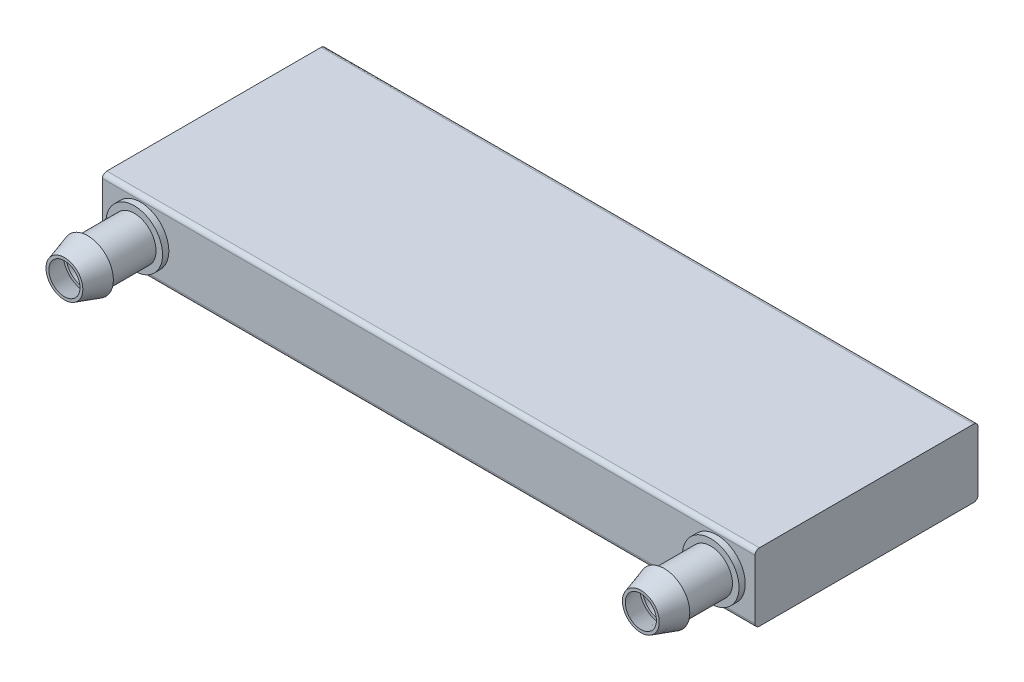
SolidWorks part; units mm, degrees
ref_plane "Front Plane" through (0, 0, 0) normal (0, 0, 1) x (1, 0, 0)
ref_plane "Top Plane" through (0, 0, 0) normal (0, 1, 0) x (1, 0, 0)
ref_plane "Right Plane" through (0, 0, 0) normal (1, 0, 0) x (0, 0, -1)
sketch "Sketch1" plane through (0, 0, 0) normal (0, 1, 0) x (1, 0, 0)
  line L1 (60, -20.5) -> (-60, -20.5)
  line L2 (60, -20.5) -> (60, 20.5)
  line L3 (60, 20.5) -> (-60, 20.5)
  line L4 (-60, -20.5) -> (-60, 20.5)
  line L5 (60, -20.5) -> (-60, 20.5) construction
  line L6 (60, 20.5) -> (-60, -20.5) construction
  point P0 (0, 0)
  dimension "D1" = 41
  dimension "D2" = 120
extrude "Boss-Extrude1" add sketch "Sketch1" along normal blind 12.5
sketch "Sketch2" plane through (0, 0, 20.5) normal (0, 0, 1) x (1, 0, 0)
  line L0 (53, 12.5) -> (53, 0) construction
  line L1 (-60, 12.5) -> (60, 12.5) construction
  line L2 (-60, 0) -> (60, 0) construction
  line L3 (60, 12.5) -> (60, 0) construction
  circle A0 centre (53, 6.25) radius 5.2
  point P8 (52.7193, 6.25)
  dimension "D1" = 10.4
  dimension "D2" = 7
extrude "Boss-Extrude2" add sketch "Sketch2" along normal blind 1.15
sketch "Sketch3" plane through (0, 0, 21.65) normal (0, 0, 1) x (1, 0, 0)
  circle A0 centre (53, 6.25) radius 4
  dimension "D1" = 8
extrude "Boss-Extrude3" add sketch "Sketch3" along normal blind 8.55
sketch "Sketch4" plane through (0, 0, 30.2) normal (0, 0, 1) x (1, 0, 0)
  circle A0 centre (53, 6.25) radius 4.7
  dimension "D1" = 9.4
extrude "Boss-Extrude4" add sketch "Sketch4" along normal blind 4.3 draft 17
mirror "Mirror1" about plane through (0, 0, 0) normal (1, 0, 0) of "Boss-Extrude4", "Boss-Extrude3", "Boss-Extrude2"
fillet "Fillet1" radius 0.8 4 edges at (0, 12.5, -20.5) (0, 12.5, 20.5) (0, 0, 20.5) (0, 0, -20.5)
shell "Shell1" thickness 0.5 removed face at (56.3854, 6.25, 34.5) removed face at (-49.6146, 6.25, 34.5)
sketch "Sketch5" plane through (0, 0, 0) normal (0, -1, 0) x (1, 0, 0)
  line L0 (0, 0) -> (-60, 0) construction
  line L2 (-60, -19.7) -> (-60, 19.7) construction
  line L3 (0, -19.7) -> (0, 19.7) construction
  line L4 (60, -19.7) -> (-60, -19.7) construction
  line L5 (-60, 19.7) -> (60, 19.7) construction
  line L6 (0, 0) -> (60, 0) construction
  line L7 (60, 19.7) -> (60, -19.7) construction
  point P2 (-30, 0)
  point P3 (30, 0)
sketch "Sketch6" plane through (0, 12.5, 0) normal (0, 1, 0) x (1, 0, 0)
  point P0 (30, 0)
  point P2 (-30, 0)
ref_point "Point1"
ref_point "Point2"
ref_point "Point3"
ref_point "Point4"
ref_axis "Axis1" through (-30, 12.5, 0) along (0, -1, 0)
ref_axis "Axis2" through (30, 12.5, 0) along (0, -1, 0)
